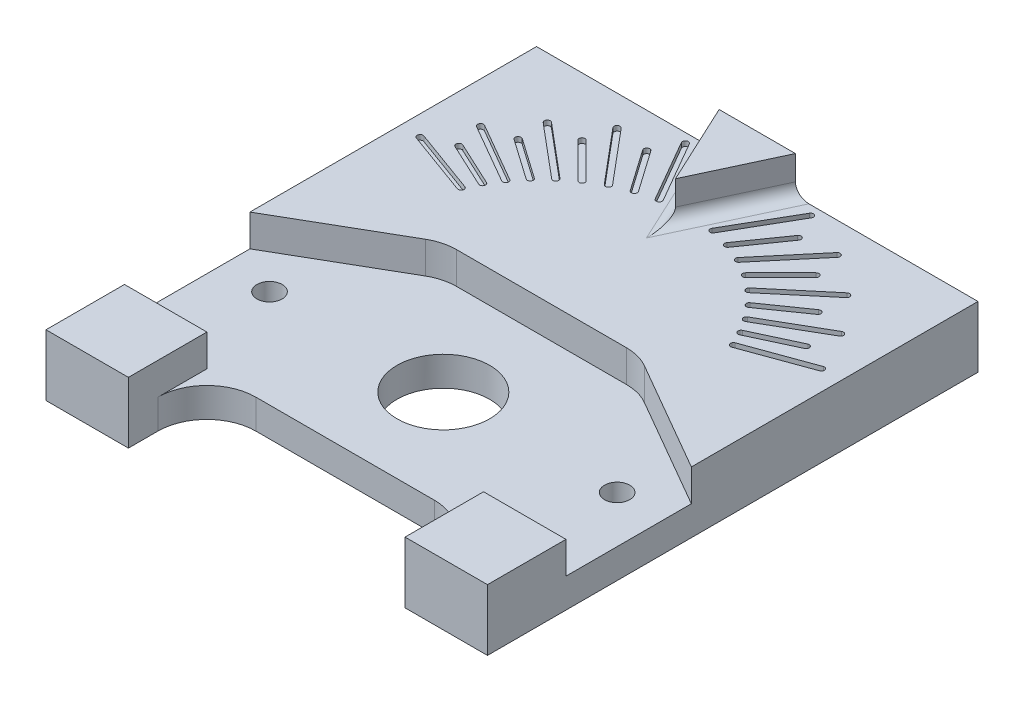
SolidWorks part; units mm, degrees
material "6061 Alloy"
ref_plane "Front" through (0, 0, 0) normal (0, 0, 1) x (1, 0, 0)
ref_plane "Top" through (0, 0, 0) normal (0, 1, 0) x (1, 0, 0)
ref_plane "Right" through (0, 0, 0) normal (1, 0, 0) x (0, 0, -1)
sketch "Sketch1" plane through (0, 0, 0) normal (0, 1, 0) x (1, 0, 0)
  line L1 (-28.575, -12.7) -> (28.575, -12.7)
  line L2 (-28.575, -12.7) -> (-28.575, 12.7)
  line L3 (-28.575, 12.7) -> (28.575, 12.7)
  line L4 (28.575, -12.7) -> (28.575, 12.7)
  line L5 (-28.575, -12.7) -> (28.575, 12.7) construction
  line L6 (-28.575, 12.7) -> (28.575, -12.7) construction
  point P0 (0, 0)
  dimension "D1" = 57.15
  dimension "D2" = 25.4
extrude "Boss-Extrude1" add sketch "Sketch1" along normal blind 3.81
sketch "Sketch2" plane through (0, 3.81, 0) normal (0, 1, 0) x (1, 0, 0)
  circle A0 centre (0, 0) radius 6
  dimension "D1" = 12
extrude "Cut-Extrude1" cut sketch "Sketch2" against normal up to next
sketch "Sketch3" plane through (0, 3.81, 0) normal (0, 1, 0) x (1, 0, 0)
  line L0 (-50, 0) -> (50, 0) construction
  line L1 (-22.5, 0) -> (22.5, 0) construction
  line L2 (0, -50) -> (0, 50) construction
  point P0 (-22.5, 0)
  point P1 (22.5, 0)
  point P6 (0, 0)
  dimension "D1" = 45
hole_wizard "#4 Clearance Hole1" positions "Sketch4" profile "Sketch6" hole size "#4" standard "ANSI Inch" end condition through all
sketch "Sketch4" plane through (0, 3.81, 0) normal (0, 1, 0) x (1, 0, 0)
  point P0 (-22.5, 0)
  point P3 (22.5, 0)
sketch "Sketch6" plane through (-22.5, 3.81, 0) normal (1, 0, 0) x (0, 0, 1)
  line L0 (0, 0) -> (0, 3.81)
  line L1 (0, 3.81) -> (1.6319, 3.81)
  line L2 (1.6319, 3.81) -> (1.6319, 0)
  line L5 (1.6319, 0) -> (0, 0)
  line L11 (0, -6.35) -> (0, 107.95) construction
  dimension "Thru Hole Dia." = 3.2639
  dimension "Thru Hole Depth" = 3.81
sketch "Sketch7" plane through (0, 3.81, 0) normal (0, 1, 0) x (1, 0, 0)
  line L0 (-21.2126, 45.4905) -> (21.2126, -45.4905) construction
  line L1 (-24.9481, -53.5015) -> (26.6541, 57.1598) construction
  line L4 (27.6119, -29.1631) -> (-4.5916, 39.8976) construction
  line L5 (27.6119, -29.1631) -> (4.5916, -39.8976) construction
  line L6 (-4.5916, 39.8976) -> (-27.6119, 29.1631) construction
  line L7 (4.5916, -39.8976) -> (-27.6119, 29.1631) construction
  line L8 (27.6119, -29.1631) -> (-27.6119, 29.1631) construction
  line L9 (-4.5916, 39.8976) -> (4.5916, -39.8976) construction
  line L10 (28.575, 12.7) -> (-28.575, 12.7) construction
  point P7 (0, 0)
  dimension "D1" = 65
  dimension "D2" = 65
  dimension "D3" = 25.4
  dimension "D4" = 76.2
ref_plane "Plane1" through (0, 12.7, 0) normal (0, 1, 0) x (1, 0, 0)
sketch "Sketch8" plane through (0, 3.81, 0) normal (0, 1, 0) x (1, 0, 0)
  line L1 (-28.575, 12.7) -> (-18.415, 12.7)
  line L10 (28.575, 12.7) -> (-28.575, 12.7) construction
  line L13 (-18.415, 12.7) -> (-18.415, 77.0545)
  line L18 (-4.5916, 39.8976) -> (27.6119, -29.1631) construction
  line L19 (-4.5916, 39.8976) -> (-27.6119, 29.1631) construction
  line L20 (27.6119, -29.1631) -> (4.5916, -39.8976) construction
  line L21 (-27.6119, 29.1631) -> (4.5916, -39.8976) construction
  line L22 (-4.5916, 39.8976) -> (4.5916, -39.8976) construction
  line L23 (27.6119, -29.1631) -> (-27.6119, 29.1631) construction
  line L24 (-84544.8649, 181307.0479) -> (84544.8649, -181307.0479) construction
  line L25 (28.575, -12.7) -> (28.575, -98.8427)
  line L26 (28.575, -98.8427) -> (18.415, -77.0545)
  line L27 (18.415, -77.0545) -> (18.415, -12.7)
  line L28 (-28.575, -12.7) -> (28.575, -12.7) construction
  line L29 (28.575, -12.7) -> (18.415, -12.7)
  line L30 (-18.415, 77.0545) -> (-28.575, 98.8427)
  line L31 (-28.575, 98.8427) -> (-28.575, 12.7)
  point P1 (0, 0)
  line M11 (28.575, 12.7) -> (-28.575, 12.7)
  dimension "D1" = 25.4
  dimension "D2" = 76.2
  dimension "D3" = 10.16
  dimension "D4" = 3.175
  dimension "D5" = 3.175
  dimension "D6" = 10.16
extrude "Boss-Extrude4" [suppressed] add sketch "Sketch8" against normal up to surface (3.81 mm away) contours L30 L31 L13 M11 up to plane "Top"
mirror "Mirror4" [suppressed] about plane through (0, 0, 0) normal (1, 0, 0)
mirror "Mirror6" [suppressed] about plane through (0, 0, 0) normal (0, 0, 1)
sketch "Sketch11" [suppressed] plane through (0, 3.81, 0) normal (0, 1, 0) x (1, 0, 0)
  line L6 (-18.415, 26.1032) -> (-28.575, 30.8409)
  line L7 (-28.575, 30.8409) -> (-28.575, 27.3376)
  line L8 (-28.575, 30.8409) -> (-28.575, -12.7) construction
  line L9 (-28.575, 27.3376) -> (-18.415, 22.6)
  line L10 (-18.415, 12.7) -> (-18.415, 26.1032) construction
  line L11 (-18.415, 22.6) -> (-18.415, 26.1032)
  dimension "D1" = 3.175
extrude "Boss-Extrude5" [suppressed] add sketch "Sketch11" along normal up to surface (8.89 mm away) up to plane "Plane1"
mirror "Mirror7" [suppressed] about plane through (0, 0, 0) normal (1, 0, 0)
mirror "Mirror8" [suppressed] about plane through (0, 0, 0) normal (0, 0, 1)
sketch "Sketch12" [suppressed] plane through (0, 3.81, 0) normal (0, 1, 0) x (1, 0, 0)
  line L19 (18.415, 12.7) -> (-18.415, 12.7)
  line L20 (18.415, 12.7) -> (18.415, 22.6)
  line L21 (18.415, 22.6) -> (-18.415, 22.6)
  line L22 (-18.415, 12.7) -> (-18.415, 22.6)
extrude "Boss-Extrude6" [suppressed] add sketch "Sketch12" against normal up to surface (3.81 mm away) up to plane "Top"
sketch "Sketch13" [suppressed] plane through (0, 3.81, 0) normal (0, 1, 0) x (1, 0, 0)
  line L0 (12.7, 12.948) -> (-12.7, 12.948)
  line L1 (-12.7, 12.948) -> (-28.575, 3.7825)
  line L2 (-28.575, 27.3376) -> (-28.575, -12.7) construction
  line L10 (28.575, -12.7) -> (28.575, 27.3376) construction
  line L11 (28.575, 3.7825) -> (12.7, 12.948)
  line L12 (0, -50) -> (0, 50) construction
  line L13 (-28.575, 3.7825) -> (-28.575, 27.3376)
  line L14 (-28.575, 27.3376) -> (-18.415, 22.6)
  line L15 (-18.415, 22.6) -> (18.415, 22.6)
  line L16 (18.415, 22.6) -> (28.575, 27.3376)
  line L17 (28.575, 27.3376) -> (28.575, 3.7825)
  point P15 (0, 12.948)
  dimension "D1" = 9.652
  dimension "D2" = 25.4
  dimension "D3" = 30
  dimension "D4" = 30
extrude "Boss-Extrude7" [suppressed] add sketch "Sketch13" along normal blind 4.1275
fillet "Fillet1" [suppressed] radius 1.5875
fillet "Fillet4" [suppressed] radius 3.175
fillet "Fillet5" [suppressed] radius 1.5875
sketch "Sketch14" plane through (0, 0, 0) normal (0, 1, 0) x (1, 0, 0)
  line L1 (28.575, -12.7) -> (17.907, -12.7)
  line L2 (28.575, -12.7) -> (28.575, -22.86)
  line L3 (28.575, -22.86) -> (17.907, -22.86)
  line L4 (17.907, -12.7) -> (17.907, -22.86)
  dimension "D1" = 10.668
  dimension "D2" = 10.16
extrude "Boss-Extrude8" [suppressed] add sketch "Sketch14" along normal up to surface (7.9375 mm away) up to face at (0, 0, 0)
mirror "Mirror9" [suppressed] about plane through (0, 0, 0) normal (1, 0, 0)
fillet "Fillet6" [suppressed] radius 3.175
fillet "Fillet7" [suppressed] radius 5.08
sketch "Sketch15" plane through (0, 0, 0) normal (0, 1, 0) x (1, 0, 0)
  line L0 (-5.9221, 12.7) -> (5.9221, 12.7)
  line L1 (-84544.8649, 181307.0479) -> (84544.8649, -181307.0479) construction
  line L2 (28.575, 12.7) -> (-28.575, 12.7) construction
  line L3 (-84548.6005, -181315.0589) -> (84550.3064, 181318.7172) construction
  line L4 (5.9221, 12.7) -> (11.8442, 25.4)
  line L5 (11.8442, 25.4) -> (-11.8442, 25.4)
  line L6 (-11.8442, 25.4) -> (-5.9221, 12.7)
  dimension "D1" = 12.7
extrude "Boss-Extrude9" [suppressed] add sketch "Sketch15" along normal up to surface (3.81 mm away) contours L5 L6 L0 L4 up to face at (-22.5, 3.81, 1.6319)
sketch "Sketch16" plane through (0, 0, 0) normal (0, 1, 0) x (1, 0, 0)
  line L0 (28.575, -12.7) -> (28.575, 12.7) construction
  line L5 (-28.575, 12.7) -> (28.575, 12.7)
  line L6 (-28.575, 12.7) -> (-28.575, 40.64)
  line L16 (-28.575, 40.64) -> (28.575, 40.64)
  line L17 (28.575, 12.7) -> (28.575, 40.64)
  dimension "D1" = 27.94
extrude "Boss-Extrude10" add sketch "Sketch16" along normal up to surface (3.81 mm away) contours L17 region at (0, 0, -26.67) up to face at (-22.5, 3.81, 1.6319)
sketch "Sketch19" plane through (0, 3.81, 3.81) normal (0, 1, 0) x (1, 0, 0)
  line L0 (-12.7, 16.51) -> (12.7, 16.51)
  line L1 (12.7, 16.51) -> (28.575, 7.3446)
  line L11 (-28.575, 7.3446) -> (-12.7, 16.51)
  line L24 (-28.575, 7.3446) -> (-28.575, 44.45)
  line L25 (28.575, 44.45) -> (28.575, 7.3446)
  line L26 (-28.575, 44.45) -> (-28.575, -8.89) construction
  line L27 (28.575, -8.89) -> (28.575, 44.45) construction
  line L28 (-22.5, 3.81) -> (22.5, 3.81) construction
  line L29 (-28.575, 44.45) -> (28.575, 44.45)
  line L30 (28.575, 44.45) -> (-28.575, 44.45) construction
  point P13 (0, 16.51)
  dimension "D1" = 25.4
  dimension "D2" = 12.7
  dimension "D3" = 30
  dimension "D4" = 30
extrude "Boss-Extrude12" add sketch "Sketch19" along normal blind 4.1275 contours L11 L0 L1 L25 L29 L24
sketch "Sketch20" plane through (0, 7.9375, 0) normal (0, 1, 0) x (1, 0, 0)
  line L0 (-4.9378, 40.64) -> (0, 40.64)
  line L2 (0, 40.64) -> (0, 30.0508)
  line L3 (0, 30.0508) -> (-4.9378, 40.64)
  line L4 (27.6119, -29.1631) -> (-4.5916, 39.8976) construction
  line L5 (-28.575, 40.64) -> (28.575, 40.64) construction
  point P3 (0, 0)
  point P4 (0, 0)
  point P9 (0, 0)
extrude "Boss-Extrude13" add sketch "Sketch20" along normal blind 4.7625
mirror "Mirror10" about plane through (0, 0, 0) normal (1, 0, 0) of "Boss-Extrude13"
sketch "Sketch21" plane through (0, 0, 0) normal (0, 1, 0) x (1, 0, 0)
  line L1 (28.575, -12.7) -> (17.907, -12.7)
  line L2 (28.575, -12.7) -> (28.575, -22.86)
  line L3 (28.575, -22.86) -> (17.907, -22.86)
  line L4 (17.907, -12.7) -> (17.907, -22.86)
  dimension "D1" = 10.668
  dimension "D2" = 10.16
extrude "Boss-Extrude14" add sketch "Sketch21" along normal up to surface (7.9375 mm away) up to face at (0, 7.9375, -25.0089)
mirror "Mirror11" about plane through (0, 0, 0) normal (1, 0, 0) of "Boss-Extrude14"
fillet "Fillet8" radius 1.5875 2 edges at (2.4689, 7.9375, -35.3454) (-2.4689, 7.9375, -35.3454)
fillet "Fillet9" radius 6.35 4 edges at (17.907, 1.905, 12.7) (-17.907, 1.905, 12.7) (12.7, 5.8737, -12.7) (-12.7, 5.8737, -12.7)
sketch "Sketch22" plane through (0, 7.9375, 0) normal (0, 1, 0) x (1, 0, 0)
  line L1 (0, 0) -> (0, 40.64) construction
  line L3 (-8.1052, 39.4385) -> (-3.481, 31.4293) construction
  line L4 (4.9378, 40.64) -> (-4.9378, 40.64) construction
  line L6 (-8.1052, 39.4385) -> (0, 25.4) construction
  line L8 (-7.7752, 39.629) -> (-3.151, 31.6198)
  line L10 (-8.4351, 39.248) -> (-3.811, 31.2388)
  line L11 (-9.7977, 36.1343) -> (0, 22.1418) construction
  line L12 (0, 19.7577) -> (-14.2459, 36.7353) construction
  line L13 (-9.7977, 36.1343) -> (-6.0396, 30.7672) construction
  line L14 (-19.372, 32.8337) -> (0, 16.5787) construction
  line L15 (-19.4039, 29.0906) -> (0, 15.5038) construction
  line L16 (-15.1366, 33.0971) -> (0, 17.9605) construction
  line L17 (-31.5032, 54.5652) -> (40.167, -69.5712) construction
  line L18 (-22.5, 0) -> (22.5, 0) construction
  line L19 (-58.9017, 84.1204) -> (32.2012, -45.988) construction
  line L20 (-69.2942, 58.1447) -> (54.9802, -46.1338) construction
  line L21 (-62.3249, 62.3249) -> (-57.2529, 57.2529) construction
  line L22 (-72.3772, 50.679) -> (-51.5561, 36.1) construction
  line L23 (-73.6149, 51.5457) -> (-64.9218, 45.4588) construction
  line L24 (-18.4296, 21.9636) -> (-10.1253, 12.0669) construction
  line L25 (-120.9015, 44.0046) -> (-88.6902, 32.2806) construction
  line L26 (-113.3877, 52.8736) -> (-83.6318, 38.9981) construction
  line L27 (-106.4909, 61.4825) -> (-78.831, 45.5131) construction
  line L28 (-23.3011, 28.1176) -> (0, 14.6647) construction
  line L29 (-25.9832, 22.9722) -> (0, 13.5151) construction
  line L30 (-22.4921, 24.5011) -> (0, 14.0129) construction
  line L31 (-10.9985, 12.7) -> (10.9985, 12.7) construction
  line L32 (-9.4856, 36.3528) -> (-5.7275, 30.9858)
  line L33 (-10.1098, 35.9158) -> (-6.3517, 30.5487)
  line L34 (-14.2459, 36.7353) -> (-8.4176, 29.7894) construction
  line L35 (-13.9541, 36.9802) -> (-8.1257, 30.0343)
  line L36 (-14.5378, 36.4904) -> (-8.7094, 29.5445)
  line L37 (-15.1366, 33.0971) -> (-10.5808, 28.5414) construction
  line L38 (-14.8672, 33.3665) -> (-10.3114, 28.8108)
  line L39 (-15.406, 32.8277) -> (-10.8502, 28.2719)
  line L40 (-19.372, 32.8337) -> (-12.5047, 27.0713) construction
  line L41 (-19.1271, 33.1256) -> (-12.2598, 27.3632)
  line L42 (-19.6169, 32.5419) -> (-12.7496, 26.7795)
  line L43 (-19.4039, 29.0906) -> (-14.1736, 25.4283) construction
  line L44 (-19.1853, 29.4027) -> (-13.9551, 25.7404)
  line L45 (-19.6224, 28.7785) -> (-14.3922, 25.1162)
  line L46 (-23.3011, 28.1176) -> (-15.5811, 23.6605) construction
  line L47 (-23.1106, 28.4476) -> (-15.3906, 23.9904)
  line L48 (-23.4916, 27.7876) -> (-15.7716, 23.3305)
  line L49 (-22.4921, 24.5011) -> (-16.7286, 21.8136) construction
  line L50 (-22.3311, 24.8464) -> (-16.5676, 22.1589)
  line L51 (-22.6531, 24.1558) -> (-16.8896, 21.4683)
  line L52 (-25.9832, 22.9722) -> (-17.6247, 19.9299) construction
  line L53 (-25.8529, 23.3302) -> (-17.4944, 20.288)
  line L54 (-26.1135, 22.6141) -> (-17.755, 19.5719)
  circle A0 centre (0, 12.7) radius 27.94 construction
  circle A1 centre (0, 12.7) radius 25.4 construction
  circle A2 centre (0, 12.7) radius 19.05 construction
  arc A3 (-7.7752, 39.629) -> (-8.4351, 39.248) centre (-8.1052, 39.4385) ccw
  arc A4 (-3.811, 31.2388) -> (-3.151, 31.6198) centre (-3.481, 31.4293) ccw
  arc A5 (-9.4856, 36.3528) -> (-10.1098, 35.9158) centre (-9.7977, 36.1343) ccw
  arc A6 (-6.3517, 30.5487) -> (-5.7275, 30.9858) centre (-6.0396, 30.7672) ccw
  arc A7 (-13.9541, 36.9802) -> (-14.5378, 36.4904) centre (-14.2459, 36.7353) ccw
  arc A8 (-8.7094, 29.5445) -> (-8.1257, 30.0343) centre (-8.4176, 29.7894) ccw
  arc A9 (-14.8672, 33.3665) -> (-15.406, 32.8277) centre (-15.1366, 33.0971) ccw
  arc A10 (-10.8502, 28.2719) -> (-10.3114, 28.8108) centre (-10.5808, 28.5414) ccw
  arc A11 (-19.1271, 33.1256) -> (-19.6169, 32.5419) centre (-19.372, 32.8337) ccw
  arc A12 (-12.7496, 26.7795) -> (-12.2598, 27.3632) centre (-12.5047, 27.0713) ccw
  arc A13 (-19.1853, 29.4027) -> (-19.6224, 28.7785) centre (-19.4039, 29.0906) ccw
  arc A14 (-14.3922, 25.1162) -> (-13.9551, 25.7404) centre (-14.1736, 25.4283) ccw
  arc A15 (-23.1106, 28.4476) -> (-23.4916, 27.7876) centre (-23.3011, 28.1176) ccw
  arc A16 (-15.7716, 23.3305) -> (-15.3906, 23.9904) centre (-15.5811, 23.6605) ccw
  arc A17 (-22.3311, 24.8464) -> (-22.6531, 24.1558) centre (-22.4921, 24.5011) ccw
  arc A18 (-16.8896, 21.4683) -> (-16.5676, 22.1589) centre (-16.7286, 21.8136) ccw
  arc A19 (-25.8529, 23.3302) -> (-26.1135, 22.6141) centre (-25.9832, 22.9722) ccw
  arc A20 (-17.755, 19.5719) -> (-17.4944, 20.288) centre (-17.6247, 19.9299) ccw
  point P40 (-9.7019, 22.2972)
  point P48 (-12.9916, 18.2436)
  point P52 (-5.7931, 35.4339)
  point P59 (-7.9186, 33.4508)
  point P65 (-11.3318, 33.2624)
  point P71 (-12.8587, 30.8192)
  point P77 (-15.9384, 29.9525)
  point P83 (-16.7887, 27.2594)
  point P89 (-19.4411, 25.889)
  point P95 (-19.6103, 23.1573)
  point P101 (-21.804, 21.451)
  point P107 (0, 0)
  point P108 (0, 0)
  dimension "D19" = 2.54
  dimension "D20" = 8.89
  dimension "D1" = 12.7
  dimension "D2" = 50
  dimension "D3" = 55
  dimension "D4" = 12.7
  dimension "D5" = 12.7
  dimension "D6" = 45
  dimension "D7" = 60
  dimension "D8" = 40
  dimension "D9" = 35
  dimension "D10" = 30
  dimension "D11" = 25
  dimension "D12" = 20
  dimension "D13" = 12.7
  dimension "D14" = 12.7
  dimension "D15" = 12.7
  dimension "D16" = 12.7
  dimension "D17" = 12.7
  dimension "D18" = 12.7
  dimension "D21" = 0.762
  dimension "D22" = 0.762
  dimension "D23" = 0.762
  dimension "D24" = 0.762
  dimension "D25" = 0.762
  dimension "D26" = 0.762
  dimension "D27" = 0.762
  dimension "D28" = 0.762
  dimension "D29" = 0.762
extrude "Cut-Extrude2" cut sketch "Sketch22" against normal blind 0.635
mirror "Mirror12" about plane through (0, 0, 0) normal (1, 0, 0) of "Cut-Extrude2"
